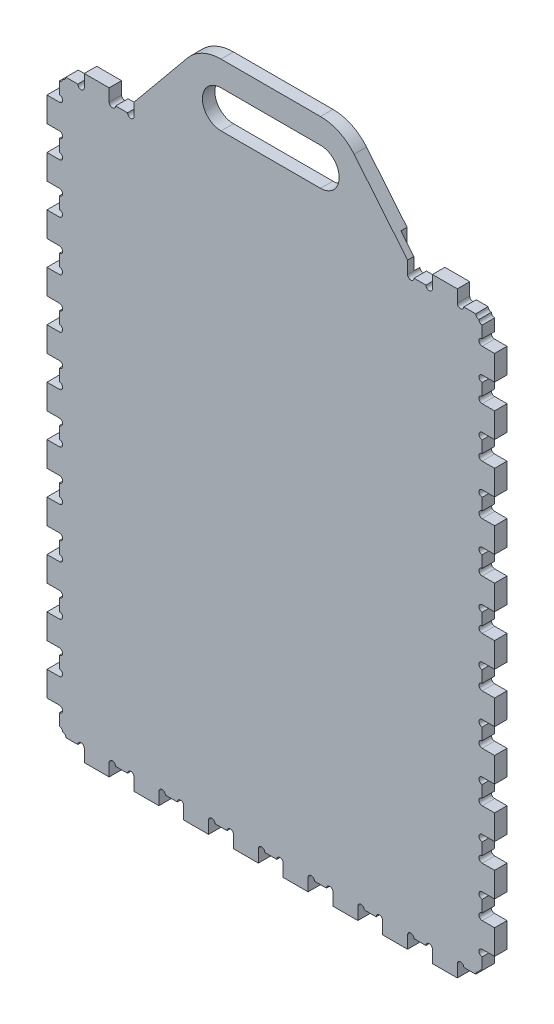
SolidWorks part; units mm, degrees
ref_plane "Front Plane" through (0, 0, 0) normal (0, 0, 1) x (1, 0, 0)
ref_plane "Top Plane" through (0, 0, 0) normal (0, 1, 0) x (1, 0, 0)
ref_plane "Right Plane" through (0, 0, 0) normal (1, 0, 0) x (0, 0, -1)
sketch "Sketch1" plane through (0, 0, 0) normal (0, 0, 1) x (1, 0, 0)
  line L1 (228.6, -304.8) -> (-228.6, -304.8)
  line L2 (228.6, -304.8) -> (228.6, 304.8)
  line L3 (228.6, 304.8) -> (-228.6, 304.8)
  line L4 (-228.6, -304.8) -> (-228.6, 304.8)
  line L5 (228.6, -304.8) -> (-228.6, 304.8) construction
  line L6 (228.6, 304.8) -> (-228.6, -304.8) construction
  line L9 (-203.2, 304.8) -> (-228.6, 304.8) construction
  point P0 (0, 0)
  dimension "D1" = 457.2
  dimension "D2" = 609.6
extrude "Boss-Extrude1" add sketch "Sketch1" along normal blind 12.7
sketch "Sketch2" plane through (0, 0, 12.7) normal (0, 0, 1) x (1, 0, 0)
  line L0 (228.6, 304.8) -> (-228.6, 304.8) construction
  line L1 (-215.9, 292.1) -> (-228.6, 292.1) construction
  line L2 (-215.9, 304.8) -> (-190.5, 304.8)
  line L3 (-215.9, 304.8) -> (-215.9, 292.1)
  line L4 (-215.9, 292.1) -> (-190.5, 292.1)
  line L5 (-190.5, 304.8) -> (-190.5, 292.1)
  line L6 (-228.6, 304.8) -> (-228.6, -304.8) construction
  circle A0 centre (-212.598, 292.1) radius 3.302
  circle A1 centre (-193.802, 292.1) radius 3.302
  line M10 (228.6, 304.8) -> (-228.6, 304.8)
  dimension "D4" = 6.604
  dimension "D5" = 6.604
  dimension "D1" = 25.4
  dimension "D2" = 12.7
  dimension "D3" = 12.7
extrude "Cut-Extrude1" cut sketch "Sketch2" against normal through all contours A1 L5 L3 A0 L4 M10 | L4 A0 | L4 A0 | L4 A1 | L4 A1 region at (-203.2, 299.0379, 12.7) region at (-212.598, 293.5014, 12.7) region at (-212.598, 290.6986, 12.7) region at (-193.802, 290.6986, 12.7) region at (-193.802, 293.5014, 12.7)
pattern_linear "LPattern1" count 9 spacing 50.8 along (1, 0, 0) of "Cut-Extrude1"
sketch "Sketch6" plane through (0, 0, 12.7) normal (0, 0, 1) x (1, 0, 0)
  line L1 (-228.6, 304.8) -> (-215.9, 304.8)
  line L2 (-228.6, 304.8) -> (-228.6, 292.1)
  line L3 (-228.6, 292.1) -> (-215.9, 292.1)
  line L4 (-215.9, 304.8) -> (-215.9, 292.1)
extrude "Cut-Extrude4" cut sketch "Sketch6" against normal through all
sketch "Sketch3" plane through (0, 0, 12.7) normal (0, 0, 1) x (1, 0, 0)
  line L0 (-228.6, 292.1) -> (-228.6, -304.8) construction
  line L1 (-228.6, 292.1) -> (-215.9, 292.1)
  line L2 (-228.6, 292.1) -> (-228.6, 266.7)
  line L3 (-228.6, 266.7) -> (-215.9, 266.7)
  line L4 (-215.9, 292.1) -> (-215.9, 266.7)
  line L5 (-215.9, 292.1) -> (-182.9158, 292.1) construction
  line L6 (-182.9158, 292.1) -> (-182.9158, 304.8) construction
  line L8 (-165.1, 304.8) -> (-190.5, 304.8) construction
  circle A0 centre (-215.9, 288.798) radius 3.302
  circle A1 centre (-215.9, 270.002) radius 3.302
  dimension "D3" = 6.604
  dimension "D4" = 6.604
  dimension "D1" = 25.4
  dimension "D2" = 12.7
  dimension "D5" = 12.7
extrude "Cut-Extrude2" cut sketch "Sketch3" against normal through all contours A1 L4 A0 L1 L2 L3 | L4 A0 | L4 A0 | L4 A1 | L4 A1 region at (-222.8379, 279.4, 12.7) region at (-214.4986, 288.798, 12.7) region at (-217.3014, 288.798, 12.7) region at (-217.3014, 270.002, 12.7) region at (-214.4986, 270.002, 12.7)
pattern_linear "LPattern2" count 12 spacing 50.8 along (0, -1, 0) of "Cut-Extrude2"
ref_plane "Plane1" through (0, 0, 0) normal (1, 0, 0) x (0, 0, -1)
ref_plane "Plane2" through (0, 0, 0) normal (0, 1, 0) x (1, 0, 0)
mirror "Mirror6" about plane through (0, 0, 0) normal (1, 0, 0) of "Cut-Extrude4"
mirror "Mirror7" about plane through (0, 0, 0) normal (0, 1, 0) of "Mirror6", "Cut-Extrude4"
mirror "Mirror1" about plane through (0, 0, 0) normal (1, 0, 0) of "LPattern2"
mirror "Mirror2" about plane through (0, 0, 0) normal (0, 1, 0) of "LPattern1"
sketch "Sketch9" plane through (0, 0, 0) normal (0, 0, -1) x (-1, 0, 0)
  line L0 (-139.7, 304.8) -> (139.7, 304.8)
  line L1 (-139.7, 304.8) -> (-114.3, 304.8) construction
  line L2 (114.3, 304.8) -> (139.7, 304.8) construction
  line L3 (139.7, 304.8) -> (139.7, 292.1) construction
  line L4 (139.7, 304.8) -> (85.1274, 371.1389)
  line L5 (50.8, 387.35) -> (-50.8, 387.35)
  line L6 (-85.1274, 371.1389) -> (-139.7, 304.8)
  line L7 (-50.8, 342.9) -> (50.8, 342.9) construction
  line L8 (-50.8, 361.95) -> (50.8, 361.95)
  line L9 (-50.8, 323.85) -> (50.8, 323.85)
  line L10 (23.5425, 342.9) -> (23.5425, 304.8) construction
  line L12 (0, 292.1) -> (0, 342.9) construction
  line L13 (6.096, 292.1) -> (-6.096, 292.1) construction
  arc A0 (-50.8, 361.95) -> (-50.8, 323.85) centre (-50.8, 342.9) ccw
  arc A1 (50.8, 323.85) -> (50.8, 361.95) centre (50.8, 342.9) ccw
  arc A2 (-50.8, 387.35) -> (-85.1274, 371.1389) centre (-50.8, 342.9) ccw
  arc A4 (85.1274, 371.1389) -> (50.8, 387.35) centre (50.8, 342.9) ccw
  arc A5 (23.5425, 307.7883) -> (27.9047, 304.8) centre (50.8, 342.9) ccw
  point P12 (0, 342.9)
  dimension "D4" = 19.05
  dimension "D1" = 101.6
  dimension "D3" = 38.1
extrude "Boss-Extrude3" add sketch "Sketch9" against normal blind 12.7 contours L4 A4 L5 A2 L6 L0 A1 L9 A0 L8 region at (110.1638, 336.1186, 0)
sketch "Sketch10" plane through (0, 0, 0) normal (0, 0, -1) x (-1, 0, 0)
  line L0 (-114.3, 304.8) -> (-88.9, 304.8) construction
  circle A0 centre (-110.998, 304.8) radius 3.302
  circle A1 centre (-92.202, 304.8) radius 3.302
  arc A2 (-114.3, 292.1) -> (-107.696, 292.1) centre (-110.998, 292.1) ccw construction
  arc A3 (-95.504, 292.1) -> (-88.9, 292.1) centre (-92.202, 292.1) ccw construction
extrude "Cut-Extrude6" cut sketch "Sketch10" against normal blind 12.7
pattern_linear "LPattern3" count 5 spacing 50.8 along (-1, 0, 0) of "Cut-Extrude6"
sketch "Sketch11" plane through (0, 0, 0) normal (0, 0, -1) x (-1, 0, 0)
  line L0 (-114.3, 241.3) -> (-215.9, 241.3) construction
  line L1 (-114.3, 241.3) -> (-101.6, 241.3)
  line L2 (-114.3, 241.3) -> (-114.3, 215.9)
  line L3 (-114.3, 215.9) -> (-101.6, 215.9)
  line L4 (-101.6, 241.3) -> (-101.6, 215.9)
  circle A0 centre (-114.3, 237.998) radius 3.302
  circle A1 centre (-114.3, 219.202) radius 3.302
  circle A2 centre (-101.6, 219.202) radius 3.302
  circle A3 centre (-101.6, 237.998) radius 3.302
  dimension "D3" = 6.604
  dimension "D1" = 12.7
  dimension "D2" = 25.4
  dimension "D4" = 101.6
extrude "Cut-Extrude7" cut sketch "Sketch11" against normal through all contours A3 L1 A0 L2 A1 L3 A2 L4 | L2 A0 | L2 A1 | L4 A2 | L4 A2 | L2 A0 | L2 L3 L4 L1 | A3 region at (112.8986, 237.998, 0) region at (107.95, 228.6, 0) region at (115.7014, 237.998, 0) region at (115.7014, 219.202, 0) region at (100.1986, 219.202, 0) region at (103.0014, 219.202, 0)
pattern_linear "LPattern4" count 10 spacing 50.8 along (0, -1, 0) of "Cut-Extrude7"
sketch "Sketch12" plane through (0, 0, 0) normal (0, 0, -1) x (-1, 0, 0)
  line L1 (-120.7835, 311.9529) -> (124.4661, 311.9529)
  line L2 (-120.7835, 311.9529) -> (-120.7835, 283.3854)
  line L3 (-120.7835, 283.3854) -> (124.4661, 283.3854)
  line L4 (124.4661, 311.9529) -> (124.4661, 283.3854)
extrude "Boss-Extrude4" add sketch "Sketch12" against normal blind 12.7
sketch "Sketch13" plane through (0, 0, 0) normal (0, 0, -1) x (-1, 0, 0)
  line L0 (-215.9, -266.7) -> (-139.7, -266.7) construction
  line L2 (-139.7, 304.8) -> (-139.7, -266.7)
  line L3 (-139.7, -266.7) -> (-126.492, -266.7)
  line L4 (-126.492, 320.8557) -> (-126.492, -266.7)
  line L5 (-139.7, -266.7) -> (-139.7, -292.1) construction
  line L6 (-139.7, 304.8) -> (-126.492, 320.8557)
  line L7 (-85.1274, 371.1389) -> (-139.7, 304.8) construction
  arc A0 (-215.9, -273.304) -> (-215.9, -266.7) centre (-215.9, -270.002) ccw construction
  arc A1 (-139.7, -292.1) -> (-146.304, -292.1) centre (-143.002, -292.1) ccw construction
  circle A2 centre (-136.398, -266.7) radius 3.302
  circle A3 centre (-129.794, -266.7) radius 3.302
  dimension "D4" = 6.604
  dimension "D1" = 13.208
  dimension "D2" = 76.2
  dimension "D3" = 25.4
extrude "Cut-Extrude8" cut sketch "Sketch13" against normal blind 6.35 contours A3 L4 L6 L2 A2 L3 | A2 | A3 region at (133.0654, 24.3788, 0)
sketch "Sketch14" plane through (0, 0, 0) normal (0, 0, -1) x (-1, 0, 0)
  line L1 (-80.0225, 252.5145) -> (-119.7852, 252.5145)
  line L2 (-80.0225, 252.5145) -> (-80.0225, -254.9574)
  line L3 (-80.0225, -254.9574) -> (-119.7852, -254.9574)
  line L4 (-119.7852, 252.5145) -> (-119.7852, -254.9574)
extrude "Boss-Extrude5" add sketch "Sketch14" against normal blind 12.7
